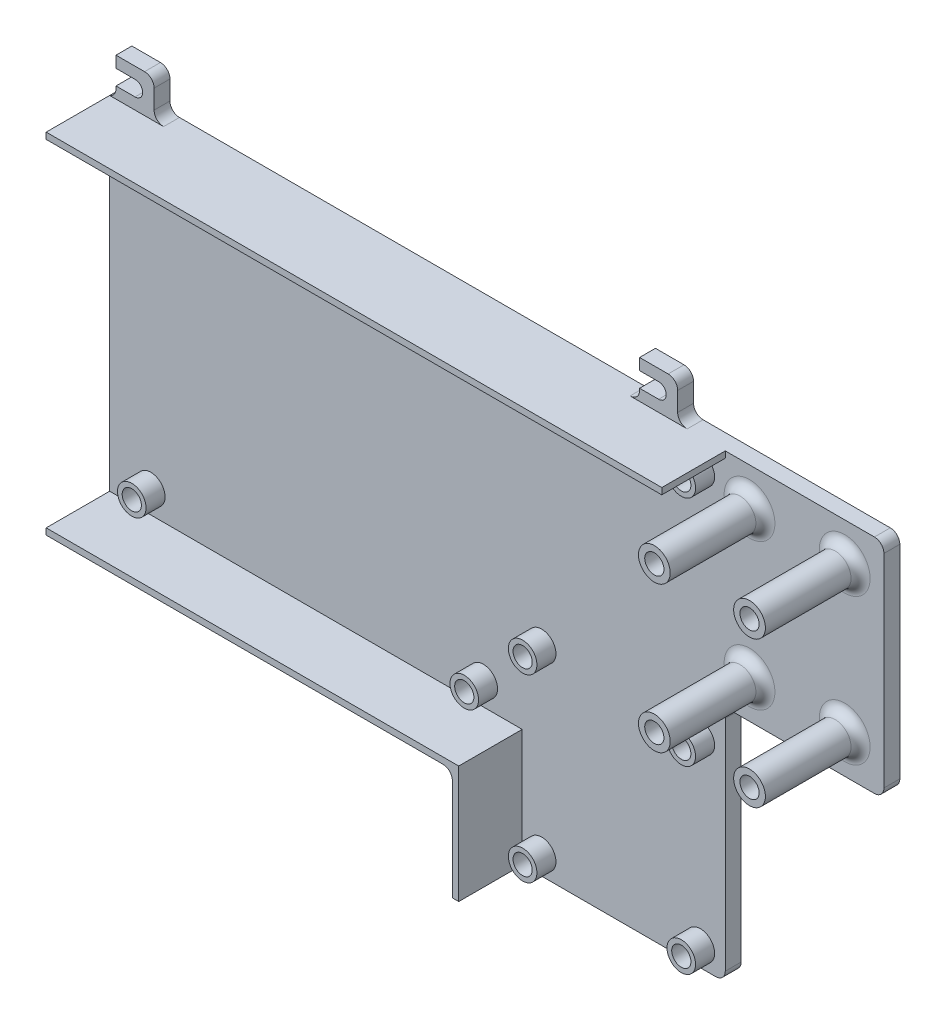
SolidWorks part; units mm, degrees
material "ABS"
ref_plane "X-Y Datum" through (0, 0, 0) normal (0, 0, 1) x (1, 0, 0)
ref_plane "X-Z Datum" through (0, 0, 0) normal (0, 1, 0) x (1, 0, 0)
ref_plane "Y-Z Datum" through (0, 0, 0) normal (1, 0, 0) x (0, 0, -1)
sketch "Sketch1" plane through (0, 0, 0) normal (0, 0, 1) x (1, 0, 0)
  line L1 (-167.3248, 270.3744) -> (-39.3248, 270.3744)
  line L2 (-167.3248, 270.3744) -> (-167.3248, 160.3744)
  line L3 (-167.3248, 160.3744) -> (-39.3248, 160.3744)
  line L4 (-39.3248, 270.3744) -> (-39.3248, 160.3744)
  line L5 (-39.3248, 270.3744) -> (26.6752, 270.3744)
  line L6 (-39.3248, 270.3744) -> (-39.3248, 125.3744)
  line L7 (-39.3248, 125.3744) -> (26.6752, 125.3744)
  line L8 (26.6752, 270.3744) -> (26.6752, 125.3744)
  line L10 (26.6752, 125.3744) -> (26.6752, 195.3744)
  line L13 (26.6752, 270.3744) -> (76.6752, 270.3744)
  line L14 (26.6752, 270.3744) -> (26.6752, 200.3744)
  line L15 (26.6752, 200.3744) -> (76.6752, 200.3744)
  line L16 (76.6752, 270.3744) -> (76.6752, 200.3744)
  dimension "D1" = 110
  dimension "D2" = 128
  dimension "D3" = 66
  dimension "D4" = 145
  dimension "D7" = 70
  dimension "D8" = 50
extrude "Boss-Extrude1" add sketch "Sketch1" along normal blind 5
sketch "Sketch2" plane through (0, 0, 5) normal (0, 0, 1) x (1, 0, 0)
  circle A1 centre (-154.3548, 262.4914) radius 3.025
  circle A2 centre (-154.3548, 262.4914) radius 4.5
  circle A6 centre (-154.3548, 169.5274) radius 4.5
  circle A7 centre (-154.3548, 169.5274) radius 3.025
  circle A8 centre (-31.1818, 131.5554) radius 4.5
  circle A9 centre (-31.1818, 131.5554) radius 3.025
  circle A10 centre (18.8182, 131.5554) radius 3.025
  circle A11 centre (18.8182, 131.5554) radius 4.5
  circle A12 centre (18.8182, 188.3054) radius 3.025
  circle A13 centre (18.8182, 188.3054) radius 4.5
  circle A14 centre (-31.1818, 188.3054) radius 4.5
  circle A15 centre (-31.1818, 188.3054) radius 3.025
  circle A16 centre (-31.1818, 261.5554) radius 3.025
  circle A17 centre (-31.1818, 261.5554) radius 4.5
  circle A18 centre (18.8182, 261.5554) radius 4.5
  circle A19 centre (18.8182, 261.5554) radius 3.025
  circle A21 centre (-49.5798, 169.5274) radius 2.1 construction
  circle A23 centre (-49.5798, 169.5274) radius 2.1
  circle A24 centre (-49.5798, 262.4914) radius 4.4118
  circle A25 centre (-49.5798, 262.4914) radius 3.025
  circle A26 centre (-49.5798, 169.5274) radius 4.5
  circle A27 centre (-49.5798, 169.5274) radius 3.025
  point P0 (-154.3548, 262.4914)
  point P1 (-44.4998, 262.4914)
  point P3 (-44.4998, 169.5274)
  point P5 (-154.3548, 169.5274)
  point P7 (18.8182, 261.5554)
  point P9 (-31.1818, 261.5554)
  point P11 (-31.1818, 188.3054)
  point P13 (-31.1818, 131.5554)
  point P15 (18.8182, 131.5554)
  point P17 (18.8182, 188.3054)
  dimension "D1" = 6.05
  dimension "D2" = 9
extrude "Boss-Extrude2" add sketch "Sketch2" along normal blind 6 contours A26 A27 | A14 A15 | A8 A9 | A11 A10 | A13 A12 | A18 A19 | A24 A25 | A2 A1 | A6 A7 | A17 A16
sketch "Sketch3" plane through (0, 0, 5) normal (0, 0, 1) x (1, 0, 0)
  line L0 (26.6752, 200.3744) -> (26.6752, 125.3744) construction
  line L1 (-167.3248, 270.3744) -> (26.6752, 270.3744)
  line L2 (-167.3248, 270.3744) -> (-167.3248, 268.3744)
  line L3 (-167.3248, 268.3744) -> (26.6752, 268.3744)
  line L4 (26.6752, 270.3744) -> (26.6752, 268.3744)
  line L6 (-167.3248, 160.3744) -> (-39.3248, 160.3744)
  line L7 (-167.3248, 160.3744) -> (-167.3248, 162.3744)
  line L8 (-167.3248, 162.3744) -> (-39.3248, 162.3744)
  line L9 (-39.3248, 160.3744) -> (-39.3248, 162.3744)
  line L10 (-39.3248, 125.3744) -> (-37.3248, 125.3744)
  line L11 (-39.3248, 125.3744) -> (-39.3248, 162.3744)
  line L12 (-39.3248, 162.3744) -> (-37.3248, 162.3744)
  line L13 (-37.3248, 125.3744) -> (-37.3248, 162.3744)
  dimension "D1" = 2
  dimension "D2" = 2
  dimension "D3" = 2
extrude "Boss-Extrude3" add sketch "Sketch3" along normal blind 20
sketch "Sketch6" plane through (0, 0, 0) normal (0, 0, -1) x (-1, 0, 0)
  line L0 (167.3248, 160.3744) -> (39.3248, 160.3744) construction
  line L1 (137.3248, 160.3744) -> (125.3248, 160.3744)
  line L2 (137.3248, 160.3744) -> (137.3248, 148.3744)
  line L3 (137.3248, 148.3744) -> (125.3248, 148.3744)
  line L4 (125.3248, 160.3744) -> (125.3248, 148.3744)
  line L5 (-26.6752, 270.3744) -> (167.3248, 270.3744) construction
  line L6 (165.3248, 270.3744) -> (153.3248, 270.3744)
  line L7 (165.3248, 270.3744) -> (165.3248, 282.3744)
  line L8 (165.3248, 282.3744) -> (153.3248, 282.3744)
  line L9 (153.3248, 270.3744) -> (153.3248, 282.3744)
  line L11 (51.3248, 160.3744) -> (39.3248, 160.3744)
  line L12 (51.3248, 160.3744) -> (51.3248, 148.3744)
  line L13 (51.3248, 148.3744) -> (39.3248, 148.3744)
  line L14 (39.3248, 160.3744) -> (39.3248, 148.3744)
  line L15 (131.3248, 160.3744) -> (131.3248, 148.3744) construction
  line L16 (0.3248, 270.3744) -> (-11.6752, 270.3744)
  line L17 (0.3248, 270.3744) -> (0.3248, 282.3744)
  line L18 (0.3248, 282.3744) -> (-11.6752, 282.3744)
  line L19 (-11.6752, 270.3744) -> (-11.6752, 282.3744)
  line L20 (167.3248, 162.3744) -> (167.3248, 160.3744) construction
  line L21 (159.3248, 282.3744) -> (159.3248, 270.3744) construction
  line L22 (-5.6752, 282.3744) -> (-5.6752, 270.3744) construction
  line L23 (45.3248, 160.3744) -> (45.3248, 148.3744) construction
  line L24 (167.3248, 268.3744) -> (167.3248, 162.3744) construction
  line L27 (-26.6752, 200.3744) -> (-26.6752, 125.3744) construction
  line L29 (39.3248, 125.3744) -> (39.3248, 160.3744) construction
  circle A0 centre (131.3248, 154.3744) radius 2 construction
  circle A1 centre (45.3248, 154.3744) radius 2 construction
  circle A2 centre (-5.6752, 276.3744) radius 2 construction
  circle A3 centre (159.3248, 276.3744) radius 2 construction
  dimension "D1" = 4
  dimension "D2" = 12
  dimension "D3" = 12
  dimension "D4" = 30
  dimension "D5" = 2
  dimension "D6" = 15
extrude "Boss-Extrude5" add sketch "Sketch6" against normal blind 5
hole_wizard "M4 Clearance Hole1" positions "Sketch9" profile "Sketch8" hole size "M4" standard "ANSI Metric" end condition through all
sketch "Sketch9" plane through (0, 0, 5) normal (0, 0, 1) x (1, 0, 0)
  line L0 (-131.3248, 160.3744) -> (-131.3248, 148.3744) construction
  point P0 (-131.3248, 154.3744)
  point P4 (-159.3248, 276.3744)
  point P7 (5.6752, 276.3744)
  point P10 (-45.3248, 154.3744)
sketch "Sketch8" plane through (-131.3248, 154.3744, 5) normal (1, 0, 0) x (0, -1, 0)
  line L0 (0, 0) -> (0, 5)
  line L1 (0, 5) -> (2.4, 5)
  line L2 (2.4, 5) -> (2.4, 0)
  line L5 (2.4, 0) -> (0, 0)
  line L11 (0, -6.35) -> (0, 107.95) construction
  dimension "Thru Hole Dia." = 4.8
  dimension "Thru Hole Depth" = 5
sketch "Sketch10" plane through (0, 0, 5) normal (0, 0, 1) x (1, 0, 0)
  line L0 (-159.3248, 278.7744) -> (-165.3248, 278.7744)
  line L1 (-159.3248, 282.3744) -> (-159.3248, 270.3744) construction
  line L2 (-165.3248, 270.3744) -> (-165.3248, 282.3744) construction
  line L3 (-159.3248, 273.9744) -> (-165.3248, 273.9744)
  line L4 (-131.3248, 156.7744) -> (-137.3248, 156.7744)
  line L5 (-131.3248, 160.3744) -> (-131.3248, 148.3744) construction
  line L6 (-137.3248, 160.3744) -> (-137.3248, 148.3744) construction
  line L7 (-131.3248, 151.9744) -> (-137.3248, 151.9744)
  line L8 (-45.3248, 156.7744) -> (-51.3248, 156.7744)
  line L9 (-45.3248, 160.3744) -> (-45.3248, 148.3744) construction
  line L10 (-51.3248, 160.3744) -> (-51.3248, 148.3744) construction
  line L11 (-45.3248, 151.9744) -> (-51.3248, 151.9744)
  line L12 (5.6752, 278.7744) -> (-0.3248, 278.7744)
  line L13 (5.6752, 282.3744) -> (5.6752, 270.3744) construction
  line L14 (-0.3248, 270.3744) -> (-0.3248, 282.3744) construction
  line L15 (5.6752, 273.9744) -> (-0.3248, 273.9744)
  line L16 (-51.3248, 148.3744) -> (-51.3248, 160.3744) construction
  line L17 (-51.3248, 148.3744) -> (-51.3248, 160.3744)
  line L20 (-137.3248, 160.3744) -> (-137.3248, 148.3744)
  line L21 (-137.3248, 148.3744) -> (-125.3248, 148.3744)
  line L22 (-125.3248, 148.3744) -> (-125.3248, 160.3744)
  line L23 (-125.3248, 160.3744) -> (-137.3248, 160.3744)
  line L24 (-137.3248, 160.3744) -> (-137.3248, 148.3744)
  line L25 (-137.3248, 148.3744) -> (-125.3248, 148.3744)
  line L26 (-125.3248, 148.3744) -> (-125.3248, 160.3744)
  line L27 (-125.3248, 160.3744) -> (-137.3248, 160.3744)
  line L28 (-0.3248, 282.3744) -> (-0.3248, 270.3744)
  line L29 (-0.3248, 270.3744) -> (11.6752, 270.3744)
  line L30 (26.6752, 125.3744) -> (26.6752, 200.3744)
  line L34 (26.6752, 268.3744) -> (-167.3248, 268.3744)
  line L35 (-167.3248, 268.3744) -> (-167.3248, 162.3744)
  line L36 (-167.3248, 162.3744) -> (-37.3248, 162.3744)
  line L37 (-37.3248, 162.3744) -> (-37.3248, 125.3744)
  line L38 (26.6752, 200.3744) -> (76.6752, 200.3744)
  line L48 (26.6752, 268.3744) -> (-167.3248, 268.3744)
  line L49 (-167.3248, 268.3744) -> (-167.3248, 162.3744)
  line L50 (-167.3248, 162.3744) -> (-37.3248, 162.3744)
  line L51 (-37.3248, 162.3744) -> (-37.3248, 125.3744)
  line L58 (11.6752, 270.3744) -> (11.6752, 282.3744)
  line L59 (11.6752, 282.3744) -> (-0.3248, 282.3744)
  line L60 (-0.3248, 282.3744) -> (-0.3248, 270.3744)
  line L61 (-0.3248, 270.3744) -> (11.6752, 270.3744)
  line L62 (11.6752, 270.3744) -> (11.6752, 282.3744)
  line L63 (11.6752, 282.3744) -> (-0.3248, 282.3744)
  line L64 (-165.3248, 282.3744) -> (-165.3248, 270.3744)
  line L65 (-165.3248, 270.3744) -> (-153.3248, 270.3744)
  line L66 (-153.3248, 270.3744) -> (-153.3248, 282.3744)
  line L67 (-153.3248, 282.3744) -> (-165.3248, 282.3744)
  line L68 (-165.3248, 282.3744) -> (-165.3248, 270.3744)
  line L69 (-165.3248, 270.3744) -> (-153.3248, 270.3744)
  line L70 (-153.3248, 270.3744) -> (-153.3248, 282.3744)
  line L71 (-153.3248, 282.3744) -> (-165.3248, 282.3744)
  line L80 (26.6752, 200.3744) -> (76.6752, 200.3744)
  line L82 (76.6752, 200.3744) -> (76.6752, 270.3744)
  line L84 (76.6752, 200.3744) -> (76.6752, 270.3744)
  line L85 (76.6752, 270.3744) -> (26.6752, 270.3744)
  line L86 (76.6752, 270.3744) -> (26.6752, 270.3744)
  line L87 (26.6752, 270.3744) -> (26.6752, 268.3744)
  line L89 (-37.3248, 125.3744) -> (26.6752, 125.3744)
  line L90 (-37.3248, 125.3744) -> (26.6752, 125.3744)
  line L94 (26.6752, 270.3744) -> (26.6752, 268.3744)
  line L95 (26.6752, 125.3744) -> (26.6752, 200.3744)
  circle A0 centre (-159.3248, 276.3744) radius 2.4 construction
  circle A1 centre (-131.3248, 154.3744) radius 2.4 construction
  circle A2 centre (-45.3248, 154.3744) radius 2.4 construction
  circle A3 centre (5.6752, 276.3744) radius 2.4 construction
  circle A4 centre (-159.3248, 276.3744) radius 2.4
  circle A5 centre (5.6752, 276.3744) radius 2.4
  circle A10 centre (-45.3248, 154.3744) radius 2.4
  circle A11 centre (-131.3248, 154.3744) radius 2.4
  dimension "D1" = 0
  dimension "D2" = 0
  dimension "D3" = 0
  dimension "D4" = 0
extrude "Cut-Extrude1" cut sketch "Sketch10" against normal through all
fillet "Fillet2" radius 3 11 edges at (-153.3248, 282.3744, 2.5) (-153.3248, 270.3744, 2.5) (-165.3248, 270.3744, 2.5) (-0.3248, 270.3744, 2.5) (11.6752, 270.3744, 2.5) (11.6752, 282.3744, 2.5) (-125.3248, 148.3744, 2.5) (-137.3248, 160.3744, 2.5) (-125.3248, 160.3744, 2.5) (-51.3248, 160.3744, 2.5) (-39.3248, 148.3744, 2.5)
fillet "Fillet3" radius 3 5 edges at (-39.3248, 160.3744, 15) (26.6752, 200.3744, 2.5) (76.6752, 270.3744, 2.5) (76.6752, 200.3744, 2.5) (26.6752, 125.3744, 2.5)
sketch "Sketch11" plane through (0, 0, 5) normal (0, 0, 1) x (1, 0, 0)
  circle A0 centre (34.3182, 258.3744) radius 5
  circle A1 centre (64.3182, 258.3744) radius 3.025
  circle A2 centre (64.3182, 212.3744) radius 3.025
  circle A3 centre (34.3182, 212.3744) radius 3.025
  circle A4 centre (34.3182, 258.3744) radius 3.025
  circle A5 centre (64.3182, 258.3744) radius 5
  circle A6 centre (64.3182, 212.3744) radius 5
  circle A7 centre (34.3182, 212.3744) radius 5
  dimension "D1" = 6.05
  dimension "D2" = 10
extrude "Boss-Extrude6" add sketch "Sketch11" along normal blind 30
fillet "Fillet4" radius 3 4 edges at (69.3182, 258.3744, 5) (39.3182, 258.3744, 5) (39.3182, 212.3744, 5) (69.3182, 212.3744, 5)
equation "\"16mmm\"=20"
